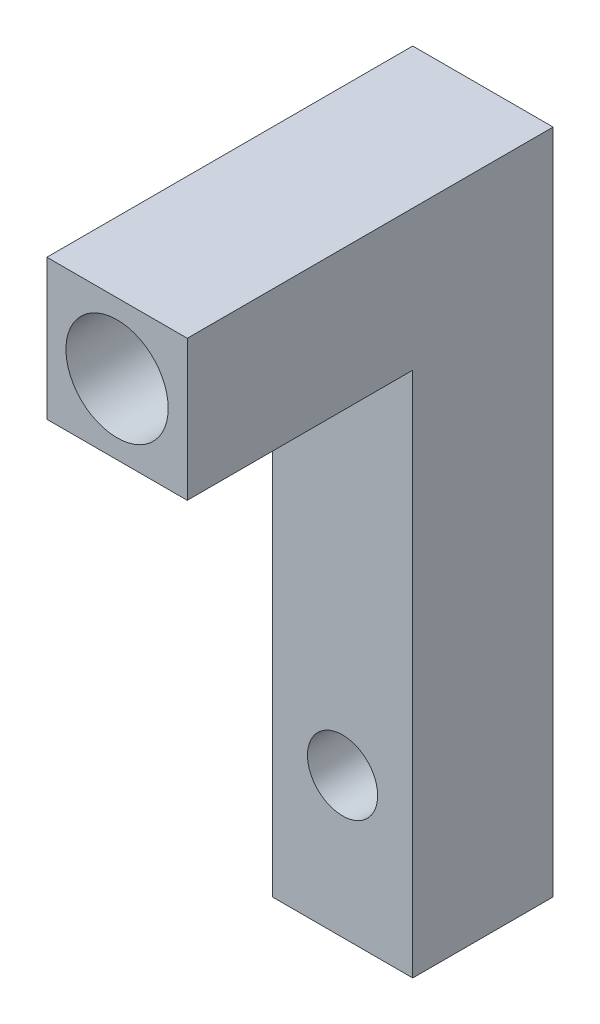
SolidWorks part; units mm, degrees
ref_plane "Front Plane" through (0, 0, 0) normal (0, 0, 1) x (1, 0, 0)
ref_plane "Top Plane" through (0, 0, 0) normal (0, 1, 0) x (1, 0, 0)
ref_plane "Right Plane" through (0, 0, 0) normal (1, 0, 0) x (0, 0, -1)
sketch "Sketch2" plane through (0, 0, 0) normal (0, 1, 0) x (1, 0, 0)
  line L1 (-25.4, -25.4) -> (25.4, -25.4)
  line L2 (-25.4, -25.4) -> (-25.4, 25.4)
  line L3 (-25.4, 25.4) -> (25.4, 25.4)
  line L4 (25.4, -25.4) -> (25.4, 25.4)
  line L5 (-25.4, -25.4) -> (25.4, 25.4) construction
  line L6 (-25.4, 25.4) -> (25.4, -25.4) construction
  point P0 (0, 0)
  dimension "D1" = 50.8
extrude "Boss-Extrude1" add sketch "Sketch2" along normal blind 241.3
sketch "Sketch3" plane through (0, 0, 25.4) normal (0, 0, 1) x (1, 0, 0)
  line L0 (0, 0) -> (0, 38.1) construction
  line L1 (-25.4, 0) -> (25.4, 0) construction
  line L2 (0, 38.1) -> (0, 50.8) construction
  circle A0 centre (0, 50.8) radius 12.7
  dimension "D3" = 25.4
  dimension "D1" = 38.1
  dimension "D2" = 12.7
extrude "Cut-Extrude1" cut sketch "Sketch3" against normal through all
sketch "Sketch4" plane through (0, 241.3, 0) normal (0, 1, 0) x (1, 0, 0)
  line L0 (-25.4, 25.4) -> (-25.4, -107) construction
  line L1 (-25.4, 25.4) -> (-25.4, -25.4) construction
  line L2 (25.4, 25.4) -> (-25.4, 25.4) construction
  line L4 (-25.4, -107) -> (25.4, -107)
  line L5 (-25.4, -107) -> (-25.4, 25.4)
  line L6 (-25.4, 25.4) -> (25.4, 25.4)
  line L7 (25.4, -107) -> (25.4, 25.4)
  line L8 (-25.4, -107) -> (25.4, 25.4) construction
  line L9 (-25.4, 25.4) -> (25.4, -107) construction
  point P9 (0, -40.8)
  dimension "D1" = 132.4
extrude "Boss-Extrude2" add sketch "Sketch4" against normal blind 50.8
sketch "Sketch5" plane through (0, 0, 107) normal (0, 0, 1) x (1, 0, 0)
  line L0 (0, 241.3) -> (0, 215.9) construction
  line L1 (-25.4, 241.3) -> (25.4, 241.3) construction
  circle A0 centre (0, 215.9) radius 18.5
  dimension "D2" = 37
  dimension "D1" = 25.4
extrude "Cut-Extrude2" cut sketch "Sketch5" against normal blind 36
